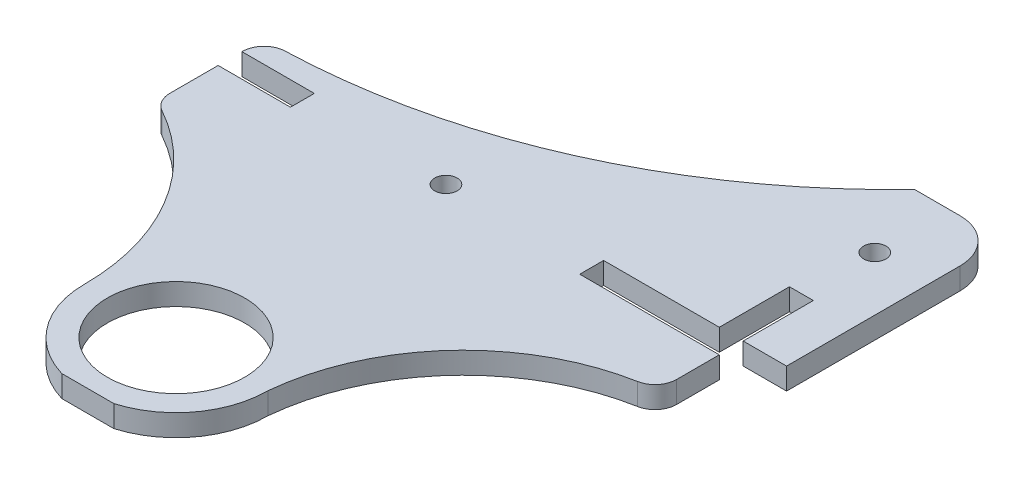
SolidWorks part; units mm, degrees
ref_plane "Alzado" through (0, 0, 0) normal (0, 0, 1) x (1, 0, 0)
ref_plane "Planta" through (0, 0, 0) normal (0, 1, 0) x (1, 0, 0)
ref_plane "Vista lateral" through (0, 0, 0) normal (1, 0, 0) x (0, 0, -1)
sketch "Croquis1" plane through (0, 0, 0) normal (0, 1, 0) x (1, 0, 0)
  line L0 (0, 38.7) -> (69.3, 38.7) construction
  line L1 (0, 0) -> (69.3, 0) construction
  line L2 (0, 0) -> (0, 38.7)
  line L3 (0, 72) -> (69.3, 72)
  line L4 (69.3, 0) -> (69.3, 38.7)
  line L5 (69.3, 51.7) -> (69.3, 72) construction
  line L8 (69.3, 51.7) -> (66, 51.7)
  line L9 (66, 42) -> (66, 51.7)
  line L11 (69.3, 38.7) -> (50, 38.7)
  line L13 (66, 42) -> (50, 42)
  line L14 (50, 38.7) -> (50, 42)
  line L15 (0, 38.7) -> (10, 38.7)
  line L17 (0, 42) -> (10, 42)
  line L18 (10, 38.7) -> (10, 42)
  line L19 (0, 42) -> (0, 72)
  line L20 (69.3, 72) -> (75.3, 72)
  line L21 (69.3, 72) -> (69.3, 51.7) construction
  line L23 (75.3, 72) -> (75.3, 52)
  line L25 (69.3, 51.7) -> (69.3, 42)
  line L26 (69.3, 42) -> (75.3, 42)
  line L27 (75.3, 52) -> (75.3, 42)
  line L28 (0, 0) -> (69.3, 0) construction
  line L29 (0, 0) -> (0, -9)
  line L30 (0, -9) -> (69.3, -9)
  line L31 (69.3, 0) -> (69.3, -9)
  circle A0 centre (30, 40.2) radius 1.55
  circle A1 centre (67.8, 61.7) radius 1.55
  circle A3 centre (29.68, 3.2) radius 9.5
  dimension "D9" = 3.1
  dimension "D13" = 6
  dimension "D14" = 3.1
  dimension "D18" = 19
  dimension "D2" = 72
  dimension "D3" = 3.3
  dimension "D4" = 13
  dimension "D5" = 16
  dimension "D6" = 3.3
  dimension "D7" = 3.3
  dimension "D8" = 10
  dimension "D10" = 30
  dimension "D11" = 20
  dimension "D12" = 1.5
  dimension "D15" = 1.5
  dimension "D16" = 10
  dimension "D17" = 40
  dimension "D19" = 35.5
  dimension "D20" = 29.68
  dimension "D21" = 30
  dimension "D22" = 9
extrude "Saliente-Extruir10" add sketch "Croquis1" along normal blind 3
sketch "Croquis3" plane through (0, 3, 0) normal (0, 1, 0) x (1, 0, 0)
  line L0 (0, 38.7) -> (0, -9) construction
  line L1 (0, 72) -> (63, 72)
  line L2 (0, 72) -> (0, 45)
  line L5 (10, 38.7) -> (0, 38.7) construction
  line L6 (69.3, -9) -> (69.3, 38.7) construction
  line L7 (69.3, 38.7) -> (50, 38.7) construction
  line L8 (0, -9) -> (69.3, -9) construction
  line L9 (69.3, -9) -> (69.3, 30.2)
  line L10 (0, -9) -> (69.3, -9)
  line L11 (0, 30.2) -> (0, -9)
  arc A0 (42.4, 3.2) -> (69.3, 30.2) centre (72.264, 0.3468) cw
  arc A1 (63, 72) -> (0, 45) centre (0, 132) cw
  arc A4 (16.96, 3.2) -> (42.4, 3.2) centre (29.68, 3.2) ccw
  arc A5 (16.96, 3.2) -> (0, 30.2) centre (-13.04, 3.1823) ccw
  circle M22 centre (67.8, 61.7) radius 1.55
  line M23 (0, 38.7) -> (0, -9)
  line M24 (0, -9) -> (69.3, -9)
  line M25 (69.3, -9) -> (69.3, 38.7)
  line M26 (69.3, 38.7) -> (50, 38.7)
  line M27 (50, 38.7) -> (50, 42)
  line M28 (50, 42) -> (66, 42)
  line M29 (66, 42) -> (66, 51.7)
  line M30 (66, 51.7) -> (69.3, 51.7)
  line M31 (69.3, 51.7) -> (69.3, 42)
  line M32 (69.3, 42) -> (75.3, 42)
  line M33 (75.3, 42) -> (75.3, 72)
  line M34 (75.3, 72) -> (0, 72)
  line M35 (0, 72) -> (0, 42)
  line M36 (0, 42) -> (10, 42)
  line M37 (10, 42) -> (10, 38.7)
  line M38 (10, 38.7) -> (0, 38.7)
  circle M39 centre (30, 40.2) radius 1.55
  dimension "D1" = 30
  dimension "D2" = 25.44
  dimension "D4" = 30
  dimension "D3" = 8.5
  dimension "D5" = 8.5
extrude "Cortar-Extruir2" cut sketch "Croquis3" against normal up to surface (3 mm away) flip side to cut contours A1 M25 M26 M27 M28 M29 M30 M31 M32 M33 M34 M35 M36 M37 M38 M23 M24 M22 M39 region at (38.7129, 3, -32.8125) up to face at (42.4875, 0, -39.7625)
fillet "Redondeo1" radius 6 1 edges at (75.3, 1.5, -72)
fillet "Redondeo2" radius 3 3 edges at (0, 1.5, -45) (69.3, 1.5, -30.2) (0, 1.5, -30.2)
